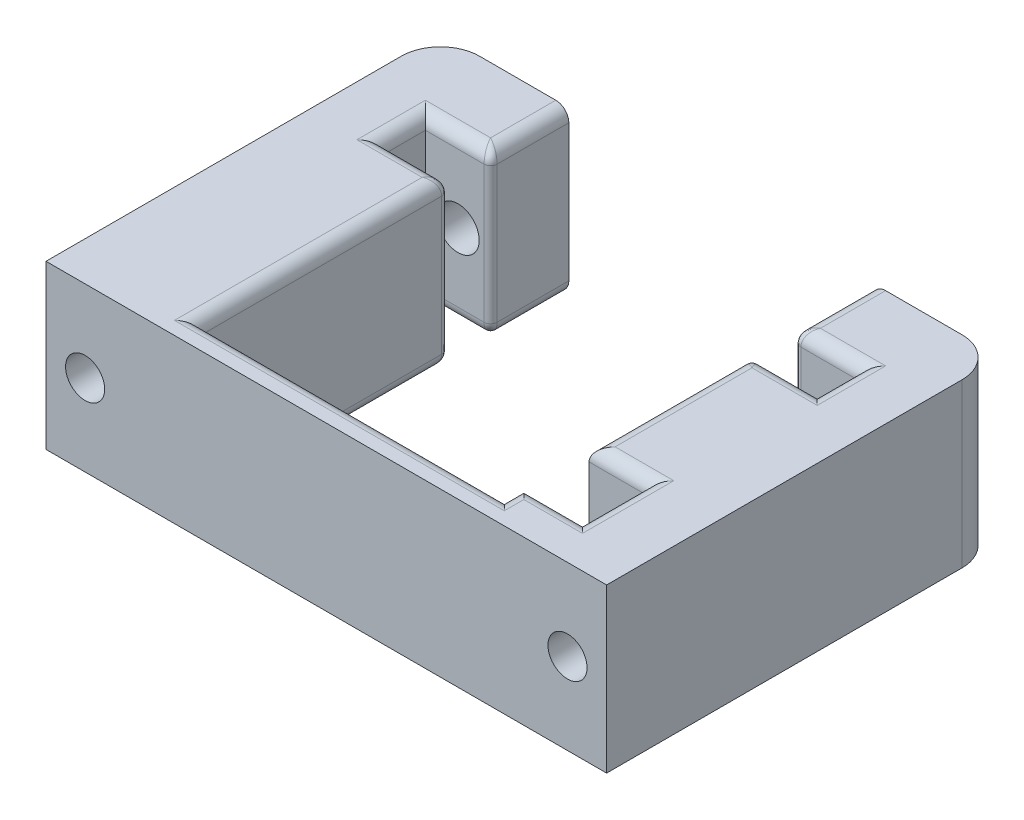
SolidWorks part; units mm, degrees
material "PLA Filament Green"
ref_plane "Front Plane" through (0, 0, 0) normal (0, 0, 1) x (1, 0, 0)
ref_plane "Top Plane" through (0, 0, 0) normal (0, 1, 0) x (1, 0, 0)
ref_plane "Right Plane" through (0, 0, 0) normal (1, 0, 0) x (0, 0, -1)
sketch "Sketch1" plane through (0, 0, 0) normal (0, 1, 0) x (1, 0, 0)
  line L1 (0, 0) -> (43, 0)
  line L2 (0, 0) -> (0, 27.25)
  line L3 (21.5, 2) -> (21.5, 0) construction
  line L5 (4.85, 21) -> (9.85, 21)
  line L6 (9.85, 21) -> (9.85, 2)
  line L7 (9.85, 2) -> (33.15, 2)
  line L9 (4.85, 21) -> (4.85, 24.25)
  line L10 (4.85, 24.25) -> (9.85, 24.25)
  line L11 (9.85, 24.25) -> (9.85, 30.25)
  line L12 (9.85, 30.25) -> (3, 30.25)
  line L13 (33.15, 30.25) -> (40, 30.25)
  line L14 (33.15, 24.25) -> (33.15, 30.25)
  line L15 (38.15, 24.25) -> (33.15, 24.25)
  line L16 (38.15, 21) -> (38.15, 24.25)
  line L17 (33.15, 21) -> (33.15, 2)
  line L18 (38.15, 21) -> (33.15, 21)
  line L20 (43, 0) -> (43, 27.25)
  arc A0 (3, 30.25) -> (0, 27.25) centre (3, 27.25) ccw
  arc A5 (40, 30.25) -> (43, 27.25) centre (40, 27.25) cw
  dimension "D8" = 3
  dimension "D1" = 6
  dimension "D2" = 2
  dimension "D3" = 43
  dimension "D4" = 3.25
  dimension "D5" = 19
  dimension "D6" = 23.3
  dimension "D7" = 5
extrude "Boss-Extrude4" add sketch "Sketch1" along normal blind 12.5 contours L6 L7 L17 L18 L16 L15 L14 L13 A5 L20 L1 L2 A0 L12 L11 L10 L9 L5
sketch "Sketch5" plane through (0, 0, -30.25) normal (0, 0, -1) x (-1, 0, 0)
  line L0 (-38.15, 12.5) -> (-33.15, 0) construction
  line L1 (-21.5, 12.5) -> (-21.5, 0) construction
  line L2 (-9.85, 12.5) -> (-33.15, 12.5) construction
  line L3 (-9.85, 0) -> (-33.15, 0) construction
  line L4 (-38.15, 0) -> (-33.15, 0)
  line L5 (-33.15, 0) -> (-33.15, 12.5)
  line L6 (-33.15, 12.5) -> (-38.15, 12.5)
  line L7 (-38.15, 12.5) -> (-38.15, 0)
  line L8 (-38.15, 0) -> (-33.15, 0)
  line L9 (-33.15, 0) -> (-33.15, 12.5) construction
  line L10 (-33.15, 12.5) -> (-38.15, 12.5) construction
  line L11 (-38.15, 12.5) -> (-38.15, 0) construction
  circle A0 centre (-35.65, 6.25) radius 1.375
  circle A1 centre (-7.35, 6.25) radius 1.375
  dimension "D2" = 2.75
  dimension "D1" = 0
extrude "Cut-Extrude1" cut sketch "Sketch5" against normal blind 18 contours A0 | A1 region at (35.65, 6.25, -30.25) region at (7.35, 6.25, -30.25)
sketch "Sketch6" plane through (0, 0, -30.25) normal (0, 0, -1) x (-1, 0, 0)
  circle A0 centre (-35.65, 6.25) radius 1.625
  circle A1 centre (-7.35, 6.25) radius 1.625
  circle A2 centre (-7.35, 6.25) radius 1.375 construction
  dimension "D1" = 3.25
extrude "Cortar-Extruir1" cut sketch "Sketch6" against normal up to next contours A1 | A0
sketch "Sketch7" plane through (0, 12.5, 0) normal (0, 1, 0) x (1, 0, 0)
  line L0 (33.15, 21) -> (33.15, 2) construction
  line L1 (33.15, 8.5) -> (37.65, 8.5)
  line L2 (33.15, 8.5) -> (33.15, 3.5)
  line L3 (33.15, 3.5) -> (37.65, 3.5)
  line L4 (37.65, 8.5) -> (37.65, 3.5)
  dimension "D1" = 4.5
  dimension "D2" = 5
  dimension "D3" = 1.5
extrude "Cut-Extrude3" cut sketch "Sketch7" against normal blind 9 contours L1 L4 L3 L2
sketch "Sketch8" plane through (0, 0, 0) normal (0, 0, 1) x (1, 0, 0)
  line L0 (37.65, 3.5) -> (37.65, 12.5) construction
  line L1 (37.65, 0) -> (37.65, 12.5) construction
  line L2 (43, 6.25) -> (0, 6.25) construction
  line L5 (43, 12.5) -> (43, 0) construction
  line L6 (0, 12.5) -> (0, 0) construction
  line L7 (0, 6.25) -> (3, 6.25) construction
  line L8 (40, 6.25) -> (43, 6.25) construction
  circle A0 centre (40, 6.25) radius 1.5
  circle A1 centre (3, 6.25) radius 1.5
  dimension "D1" = 3
  dimension "D2" = 37
extrude "Cut-Extrude4" cut sketch "Sketch8" against normal blind 10.5 contours A0 | A1
fillet "Fillet2" radius 1 2 edges at (4.5, 6.25, -10.5) (41.5, 6.25, -10.5)
fillet "Fillet4" radius 1 27 edges at (7.35, 12.5, -21) (4.85, 12.5, -22.625) (7.35, 12.5, -24.25) (21.5, 12.5, -2) (35.4, 12.5, -3.5) (35.4, 12.5, -8.5) (35.65, 12.5, -21) (35.65, 12.5, -24.25) (38.15, 12.5, -22.625) (9.85, 12.5, -11.5) (9.85, 12.5, -27.25) (33.15, 12.5, -14.75) (33.15, 12.5, -27.25) (33.15, 12.5, -2.75) (33.15, 0, -27.25) (35.65, 0, -24.25) (38.15, 0, -22.625) (35.65, 0, -21) (33.15, 0, -11.5) (21.5, 0, -2) (9.85, 0, -27.25) (7.35, 0, -24.25) (4.85, 0, -22.625) (7.35, 0, -21) (9.85, 0, -11.5) (37.65, 3.5, -6) (37.65, 12.5, -6)
fillet "Redondeo1" radius 0.5 12 edges at (9.5571, 12.2071, -24.5429) (9.5571, 0.2929, -24.5429) (33.4429, 12.2071, -24.5429) (33.4429, 0.2929, -24.5429) (33.4429, 12.2071, -20.7071) (33.15, 6.25, -21) (9.5571, 12.2071, -20.7071) (9.5571, 0.2929, -20.7071) (9.85, 6.25, -24.25) (33.15, 6.25, -24.25) (33.4429, 0.2929, -20.7071) (9.85, 6.25, -21)
